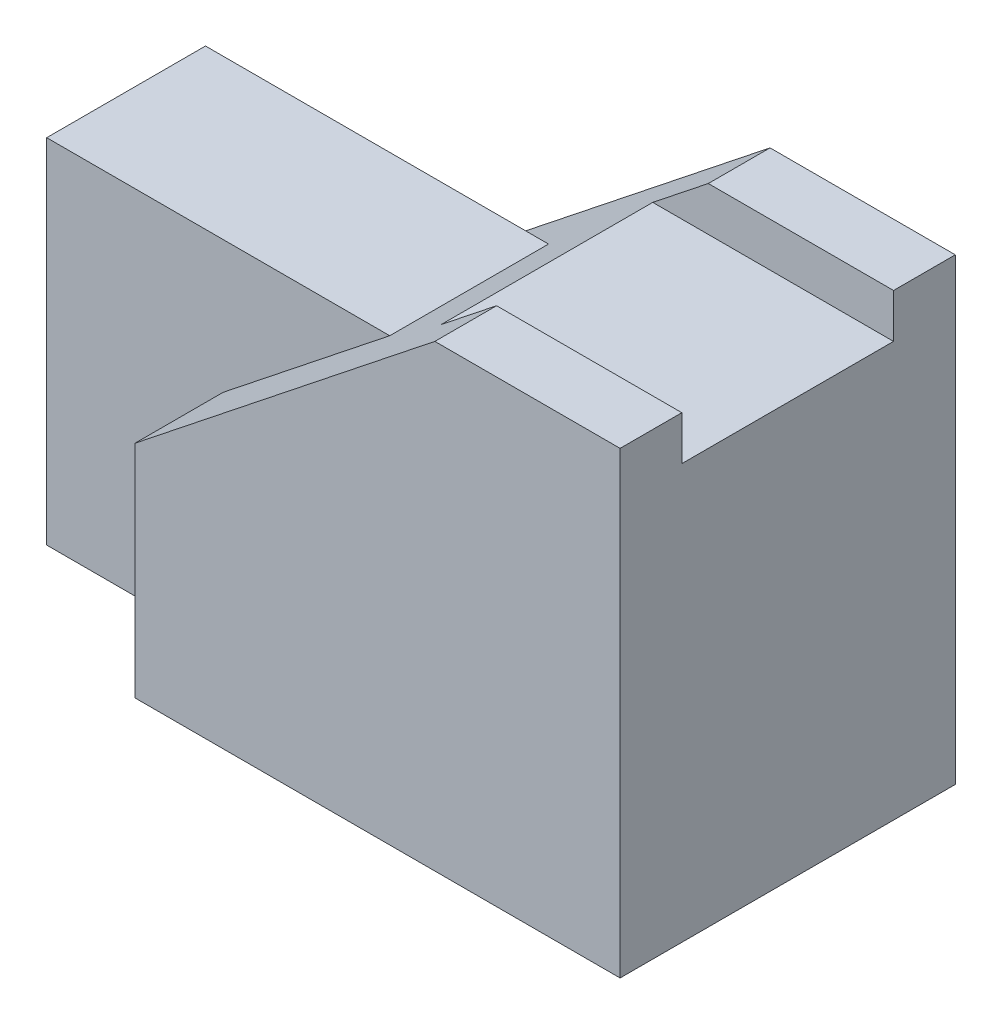
SolidWorks part; units mm, degrees
ref_plane "Front Plane" through (0, 0, 0) normal (0, 0, 1) x (1, 0, 0)
ref_plane "Top Plane" through (0, 0, 0) normal (0, 1, 0) x (1, 0, 0)
ref_plane "Right Plane" through (0, 0, 0) normal (1, 0, 0) x (0, 0, -1)
sketch "Sketch1" plane through (0, 0, 0) normal (0, 0, 1) x (1, 0, 0)
  line L0 (-35.5701, -29.1262) -> (19.4299, -29.1262)
  line L1 (19.4299, -29.1262) -> (19.4299, 22.8738)
  line L2 (19.4299, 22.8738) -> (-1.5701, 22.8738)
  line L3 (-35.5701, -29.1262) -> (-35.5701, -4.1262)
  line L4 (-35.5701, -4.1262) -> (-1.5701, 22.8738)
  line L5 (-35.5701, -29.1262) -> (-55.5701, -29.1262)
  line L6 (-55.5701, -29.1262) -> (-55.5701, 10.8738)
  line L7 (-55.5701, 10.8738) -> (-16.6812, 10.8738)
extrude "Boss-Extrude1" add sketch "Sketch1" along normal blind 19 and the other way blind 19 contours L4 L3 L0 L1 L2 region at (-4.9795, -6.3761, 0)
extrude "Boss-Extrude2" add sketch "Sketch1<3>" along normal blind 9 and the other way blind 9 contours L7 L6 L5 L3 L4 region at (-43.1184, -6.8696, 0)
sketch "Sketch1<3>" plane through (0, 0, 0) normal (0, 0, 1) x (1, 0, 0) same geometry as "Sketch1"
sketch "Sketch2" plane through (19.4299, 0, 0) normal (1, 0, 0) x (0, 0, -1)
  line L0 (-12, 22.8738) -> (12, 22.8738)
  line L1 (19, 22.8738) -> (-19, 22.8738) construction
  line L2 (-12, 22.8738) -> (-12, 17.8738)
  line L3 (-12, 17.8738) -> (12, 17.8738)
  line L4 (12, 17.8738) -> (12, 22.8738)
extrude "Cut-Extrude2" cut sketch "Sketch2" against normal blind 76
